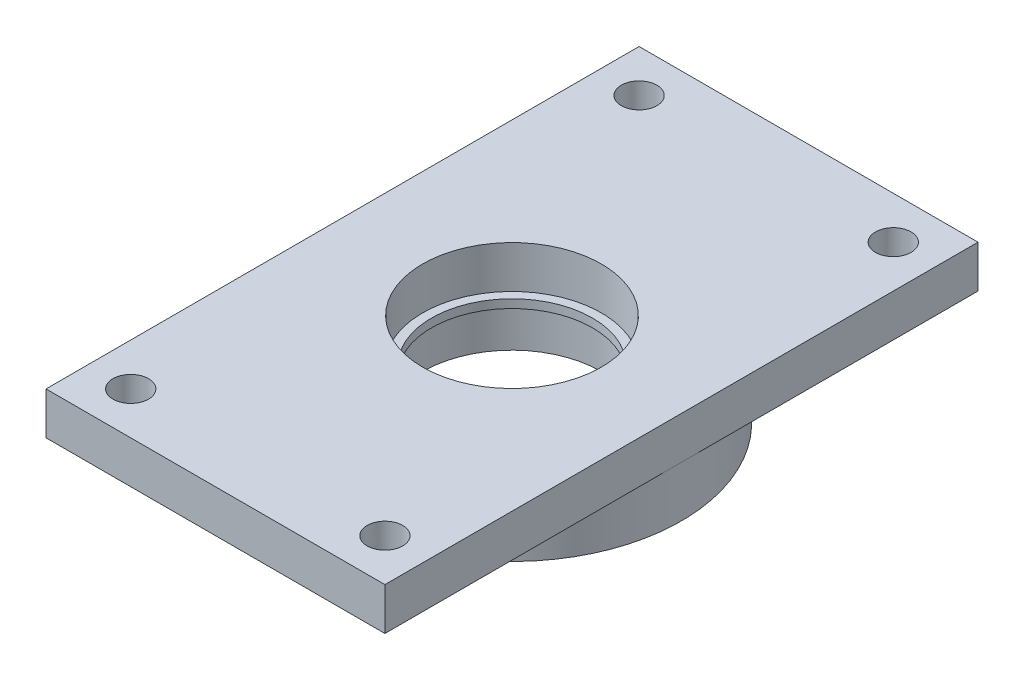
SolidWorks part; units mm, degrees
ref_plane "前视基准面" through (0, 0, 0) normal (0, 0, 1) x (1, 0, 0)
ref_plane "上视基准面" through (0, 0, 0) normal (0, 1, 0) x (1, 0, 0)
ref_plane "右视基准面" through (0, 0, 0) normal (1, 0, 0) x (0, 0, -1)
sketch "草图1" plane through (0, 0, 0) normal (0, 1, 0) x (1, 0, 0)
  line L0 (0, 0) -> (0, -58.7848) construction
  line L1 (-20, 35) -> (20, 35)
  line L2 (-20, 35) -> (-20, -35)
  line L3 (-20, -35) -> (20, -35)
  line L4 (20, 35) -> (20, -35)
  line L5 (-20, 35) -> (20, -35) construction
  line L6 (-20, -35) -> (20, 35) construction
  line L7 (0, 0) -> (35.3627, 0) construction
  line L8 (-15, -58.7848) -> (-15, 35) construction
  circle A0 centre (-15, -30) radius 2.1
  circle A1 centre (15, -30) radius 2.1
  circle A2 centre (15, 30) radius 2.1
  circle A3 centre (-15, 30) radius 2.1
  point P0 (0, 0)
  dimension "D5" = 4.2
  dimension "D1" = 70
  dimension "D2" = 40
  dimension "D3" = 5
  dimension "D4" = 5
  dimension "D6" = 60
  dimension "D7" = 30
extrude "凸台-拉伸1" add sketch "草图1" along normal blind 11
sketch "草图2" plane through (0, 11, 0) normal (0, 1, 0) x (1, 0, 0)
  circle A0 centre (0, 0) radius 9.5
  dimension "D1" = 19
extrude "切除-拉伸1" cut sketch "草图2" against normal blind 11
sketch "草图3" plane through (0, 11, 0) normal (0, 1, 0) x (1, 0, 0)
  circle A0 centre (0, 0) radius 10.55
  dimension "D1" = 21.1
extrude "切除-拉伸2" cut sketch "草图3" against normal blind 5
sketch "草图4" plane through (0, 0, 0) normal (0, -1, 0) x (1, 0, 0)
  circle A0 centre (0, 0) radius 10.55
  dimension "D1" = 21.1
extrude "切除-拉伸3" cut sketch "草图4" against normal blind 5
sketch "草图5" plane through (0, 0, 0) normal (0, -1, 0) x (1, 0, 0)
  line L0 (-20, 35) -> (20, 35) construction
  line L1 (20, 35) -> (20, -35) construction
  line L2 (20, -35) -> (-20, -35) construction
  line L3 (-20, -35) -> (-20, 35) construction
  line L4 (-20, 35) -> (20, 35)
  line L5 (20, 35) -> (20, -35)
  line L6 (20, -35) -> (-20, -35)
  line L7 (-20, -35) -> (-20, 35)
  circle A0 centre (0, 0) radius 20
  line M7 (20, -35) -> (20, 35)
  line M8 (20, 35) -> (-20, 35)
  line M9 (-20, 35) -> (-20, -35)
  line M10 (-20, -35) -> (20, -35)
  circle M11 centre (-15, 30) radius 2.1
  circle M12 centre (15, 30) radius 2.1
  circle M13 centre (15, -30) radius 2.1
  circle M14 centre (-15, -30) radius 2.1
extrude "切除-拉伸4" cut sketch "草图5" against normal up to surface (6 mm away) contours A0 L7 M10 M7 M14 M13 | A0 L5 M8 M9 M11 M12 region at (0, 0, 24.6453) region at (0, 0, -24.6453) up to face at (0, 6, 10.55)
